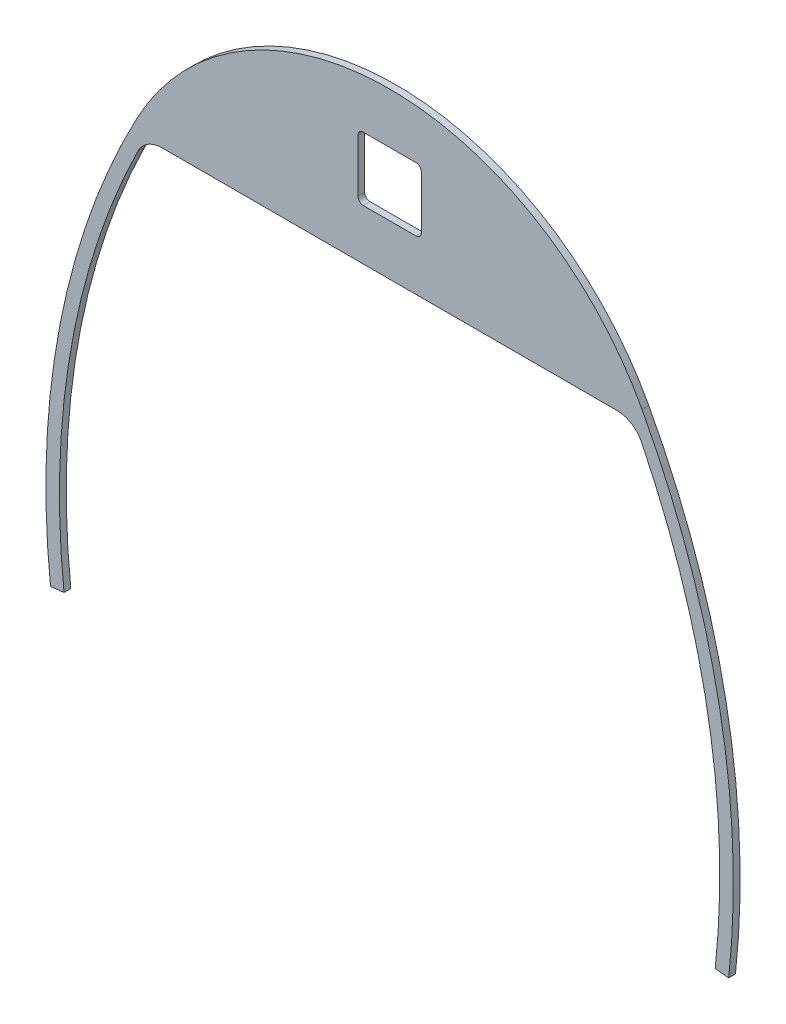
SolidWorks part; units mm, degrees
material "Zoltek Panex 33"
ref_plane "Front Plane" through (0, 0, 0) normal (0, 0, 1) x (1, 0, 0)
ref_plane "Top Plane" through (0, 0, 0) normal (0, 1, 0) x (1, 0, 0)
ref_plane "Right Plane" through (0, 0, 0) normal (1, 0, 0) x (0, 0, -1)
sketch "Sketch1" plane through (0, 0, 0) normal (0, 0, 1) x (1, 0, 0)
  line L8 (-152.4, 0) -> (152.4, 0) construction
  line L9 (-118.1286, 209.55) -> (118.1286, 209.55)
  line L10 (-114.3, 203.2) -> (114.3, 203.2)
  line L21 (-158.7119, -0.6946) -> (-152.4, 0)
  line L22 (152.4, 0) -> (158.7119, -0.6946)
  arc A0 (114.3, 203.2) -> (152.4, 0) centre (-201.0662, 38.897) cw
  arc A1 (-114.3, 203.2) -> (-152.4, 0) centre (201.0662, 38.897) ccw
  arc A2 (-118.1286, 209.55) -> (-158.7119, -0.6946) centre (201.0662, 38.897) ccw
  arc A3 (118.1286, 209.55) -> (158.7119, -0.6946) centre (-201.0662, 38.897) cw
  arc A4 (-119.9315, 206.134) -> (-158.7119, -0.6946) centre (201.0662, 38.897) ccw construction
  arc A5 (119.9315, 206.134) -> (158.7119, -0.6946) centre (-201.0662, 38.897) cw construction
  arc A6 (114.3, 203.2) -> (152.4, 0) centre (-201.0662, 38.897) cw construction
  arc A7 (-114.3, 203.2) -> (-152.4, 0) centre (201.0662, 38.897) ccw construction
  arc A8 (-118.1286, 209.55) -> (118.1286, 209.55) centre (0, 146.3942) cw
  point P0 (0, 0)
  point P13 (0, 203.2)
  dimension "D7" = 304.8
  dimension "D2" = 355.6
  dimension "D3" = 203.2
  dimension "D6" = 228.6
  dimension "D1" = 6.35
  dimension "D4" = 6.35
  dimension "D5" = 6.35
extrude "Boss-Extrude1" add sketch "Sketch1" along normal blind 3.175 contours A8 L9 | A2 L21 A1 L10 A0 L22 A3 L9 region at (0, 238.6272, 0)
ref_plane "Plane3" through (160.8838, 0, 0) normal (1, 0, 0) x (0, 0, -1)
sketch "Sketch2" plane through (0, 0, 3.175) normal (0, 0, 1) x (1, 0, 0)
  line L0 (0, 203.2) -> (0, 280.3458) construction
  line L1 (-14.859, 256.6319) -> (14.859, 256.6319)
  line L2 (-14.859, 256.6319) -> (-14.859, 226.9139)
  line L3 (-14.859, 226.9139) -> (14.859, 226.9139)
  line L4 (14.859, 256.6319) -> (14.859, 226.9139)
  line L5 (-14.859, 256.6319) -> (14.859, 226.9139) construction
  line L6 (-14.859, 226.9139) -> (14.859, 256.6319) construction
  line L7 (-114.3, 203.2) -> (114.3, 203.2) construction
  arc A0 (118.1286, 209.55) -> (-118.1286, 209.55) centre (0, 146.3942) ccw construction
  point P0 (0, 241.7729)
  point P15 (0, 241.7729)
  dimension "D1" = 29.718
  dimension "D2" = 29.718
extrude "Cut-Extrude1" cut sketch "Sketch2" against normal up to next
fillet "Fillet1" radius 2.54 4 edges at (14.859, 226.9139, 1.5875) (14.859, 256.6319, 1.5875) (-14.859, 256.6319, 1.5875) (-14.859, 226.9139, 1.5875)
fillet "Fillet2" radius 12.7 2 edges at (114.3, 203.2, 1.5875) (-114.3, 203.2, 1.5875)
sketch "Sketch3" plane through (0, 0, 0) normal (0, 0, 1) x (1, 0, 0)
  line L0 (-82.55, 115.9307) -> (82.55, 115.9307) construction
  circle A0 centre (-82.55, 115.9307) radius 41.275
  circle A1 centre (0, 115.9307) radius 41.275
  circle A2 centre (82.55, 115.9307) radius 41.275
  circle A3 centre (-41.275, 187.4211) radius 41.275
  circle A4 centre (41.275, 187.4211) radius 41.275
  circle A5 centre (41.275, 44.4403) radius 41.275
  circle A6 centre (-41.275, 44.4403) radius 41.275
  point P10 (2.36, 123.0107)
  point P11 (0, 115.9307)
  dimension "D1" = 82.55
